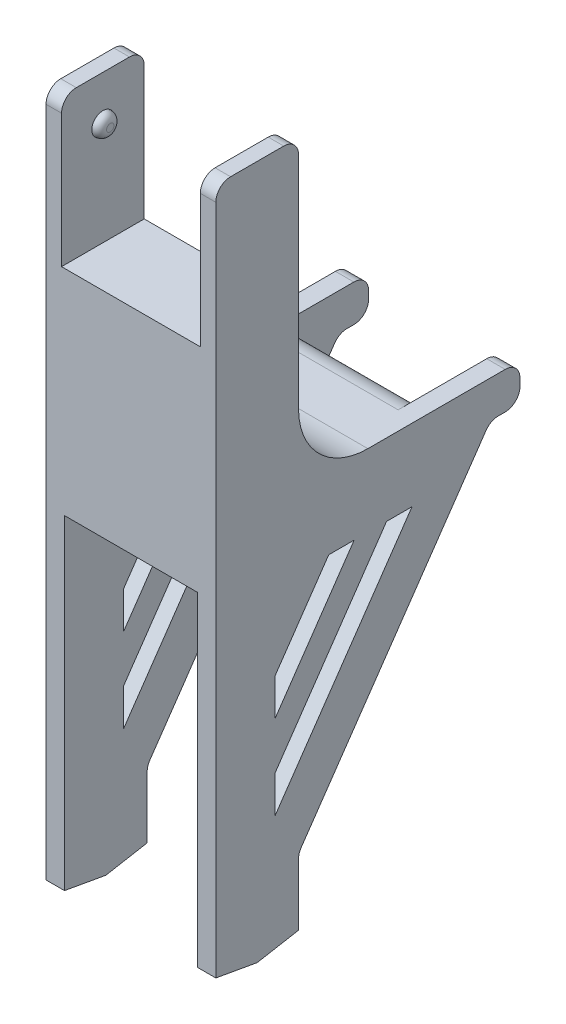
SolidWorks part; units mm, degrees
ref_plane "Front Plane" through (0, 0, 0) normal (0, 0, 1) x (1, 0, 0)
ref_plane "Top Plane" through (0, 0, 0) normal (0, 1, 0) x (1, 0, 0)
ref_plane "Right Plane" through (0, 0, 0) normal (1, 0, 0) x (0, 0, -1)
sketch "Szkic1" plane through (0, 0, 0) normal (1, 0, 0) x (0, 0, -1)
  line L2 (0, 0) -> (-10.3, 0)
  line L5 (-15, 4.7) -> (-15, 20.6)
  line L6 (-15, 20.6) -> (-20.6, 20.6)
  line L7 (-20.6, 20.6) -> (-20.6, -21.4)
  line L8 (0, 0) -> (0, -2.5)
  line L9 (0, -2.5) -> (-2, -2.5)
  line L10 (-2, -2.5) -> (-15, -21.4)
  line L11 (-15, -21.4) -> (-15, -25.9)
  line L13 (-20.6, -25.9) -> (-20.6, -21.4)
  line L20 (-20.6, -25.9) -> (-17.8, -26.4)
  line L21 (-17.8, -26.4) -> (-15, -25.9)
  arc A0 (-15, 4.7) -> (-10.3, 0) centre (-10.3, 4.7) ccw
  point P11 (0, 0)
  point P15 (-10.3, 4.7)
  dimension "D5" = 2.5
  dimension "D7" = 4.7
  dimension "D1" = 42
  dimension "D2" = 20.6
  dimension "D3" = 15.9
  dimension "D4" = 5.6
  dimension "D6" = 2
  dimension "D8" = 18.9
  dimension "D9" = 4.5
  dimension "D10" = 0.5
  dimension "D11" = 4.5
extrude "Dodanie-wyciągnięcie1" add sketch "Szkic1" along normal blind 11.5
ref_plane "Płaszczyzna dolna" through (0, 0, 20.6) normal (0, 0, 1) x (1, 0, 0)
sketch "Szkic2" plane through (0, 0, 20.6) normal (0, 0, 1) x (1, 0, 0)
  line L0 (5.75, 20.6) -> (5.75, -25.9) construction
  line L1 (11.5, 20.6) -> (0, 20.6) construction
  line L4 (10.45, 10.6) -> (1.05, 10.6)
  line L5 (10.45, 10.6) -> (10.45, 20.6)
  line L6 (10.45, 20.6) -> (1.05, 20.6)
  line L7 (1.05, 10.6) -> (1.05, 20.6)
  line L8 (10.45, 10.6) -> (1.05, 20.6) construction
  line L9 (10.45, 20.6) -> (1.05, 10.6) construction
  line L10 (10.25, -3.9) -> (1.25, -3.9)
  line L11 (10.25, -3.9) -> (10.25, -28.2703)
  line L12 (10.25, -28.2703) -> (1.25, -28.2703)
  line L13 (1.25, -3.9) -> (1.25, -28.2703)
  line L14 (10.25, -3.9) -> (1.25, -28.2703) construction
  line L15 (10.25, -28.2703) -> (1.25, -3.9) construction
  point P6 (5.75, 15.6)
  point P11 (5.75, -14.9)
  dimension "D1" = 9.4
  dimension "D2" = 10
  dimension "D3" = 9
  dimension "D4" = 11
extrude "Wytnij-wyciągnięcie1" cut sketch "Szkic2" against normal through all
ref_plane "Płaszczyzna boczna" through (11.5, 0, 0) normal (1, 0, 0) x (0, 0, -1)
sketch "Szkic3" plane through (11.5, 0, 0) normal (1, 0, 0) x (0, 0, -1)
  line L0 (-16.6, -12.7056) -> (-16.6, -10.1985)
  line L1 (-16.6, -10.1985) -> (-12.9555, -4.9)
  line L2 (-12.9555, -4.9) -> (-11.2311, -4.9)
  line L3 (-11.2311, -4.9) -> (-16.6, -12.7056)
  line L4 (-16.6, -15.8972) -> (-16.6, -18.4043)
  line L5 (-16.6, -18.4043) -> (-7.3113, -4.9)
  line L6 (-7.3113, -4.9) -> (-9.0358, -4.9)
  line L7 (-9.0358, -4.9) -> (-16.6, -15.8972)
  line L8 (-15, -21.4) -> (-2, -2.5) construction
  line L10 (-20.6, 6.325) -> (-20.6, -6.325) construction
  dimension "D1" = 4
  dimension "D2" = 21
extrude "Wytnij-wyciągnięcie2" cut sketch "Szkic3" against normal through all both and the other way through all
ref_plane "Płaszczyzna3" through (0, 0, 0) normal (0, 1, 0) x (1, 0, 0)
sketch "Szkic4" plane through (0, 0, 0) normal (0, 1, 0) x (1, 0, 0)
  line L0 (5.75, -5) -> (5.75, 0) construction
  line L2 (11.5, 0) -> (0, 0) construction
  line L4 (1.25, -5) -> (10.25, -5)
  line L5 (1.25, -5) -> (1.25, 0)
  line L6 (1.25, 0) -> (10.25, 0)
  line L7 (10.25, -5) -> (10.25, 0)
  line L8 (1.25, -5) -> (10.25, 0) construction
  line L9 (1.25, 0) -> (10.25, -5) construction
  point P6 (5.75, -2.5)
  dimension "D1" = 9
  dimension "D2" = 5
extrude "Wytnij-wyciągnięcie3" cut sketch "Szkic4" against normal blind 10
fillet "Zaokrąglenie1" radius 2 2 edges at (5.75, -3.9, 5) (5.75, 0, 5)
fillet "Zaokrąglenie2" radius 1 12 edges at (0.625, 0, 0) (0.625, -2.5, 0) (10.875, -2.5, 0) (10.875, 0, 0) (10.975, 20.6, 20.6) (10.975, 20.6, 15) (0.525, 20.6, 20.6) (0.525, 20.6, 15) (0.625, -2.5, 2) (10.875, -2.5, 2) (0.625, -21.4, 15) (10.875, -21.4, 15)
ref_plane "Płaszczyzna4" through (10.45, 0, 0) normal (-1, 0, 0) x (0, 0, 1)
sketch "Szkic5" plane through (10.45, 0, 0) normal (-1, 0, 0) x (0, 0, 1)
  line L3 (17.8, 20.6) -> (17.8, 10.6) construction
  line L4 (16, 20.6) -> (19.6, 20.6) construction
  line L5 (15, 10.6) -> (20.6, 10.6) construction
  circle A0 centre (17.8, 17.6) radius 0.75
  dimension "D1" = 1.5
  dimension "D2" = 3
extrude "Dodanie-wyciągnięcie2" add sketch "Szkic5" along normal blind 0.5
fillet "Zaokrąglenie3" radius 0.5 1 edges at (9.95, 16.85, 17.8)
ref_plane "Płaszczyzna5" through (5.75, 0, 0) normal (1, 0, 0) x (0, 0, -1)
mirror "Lustro2" about plane through (5.75, 0, 0) normal (1, 0, 0) of bodies 113 115
